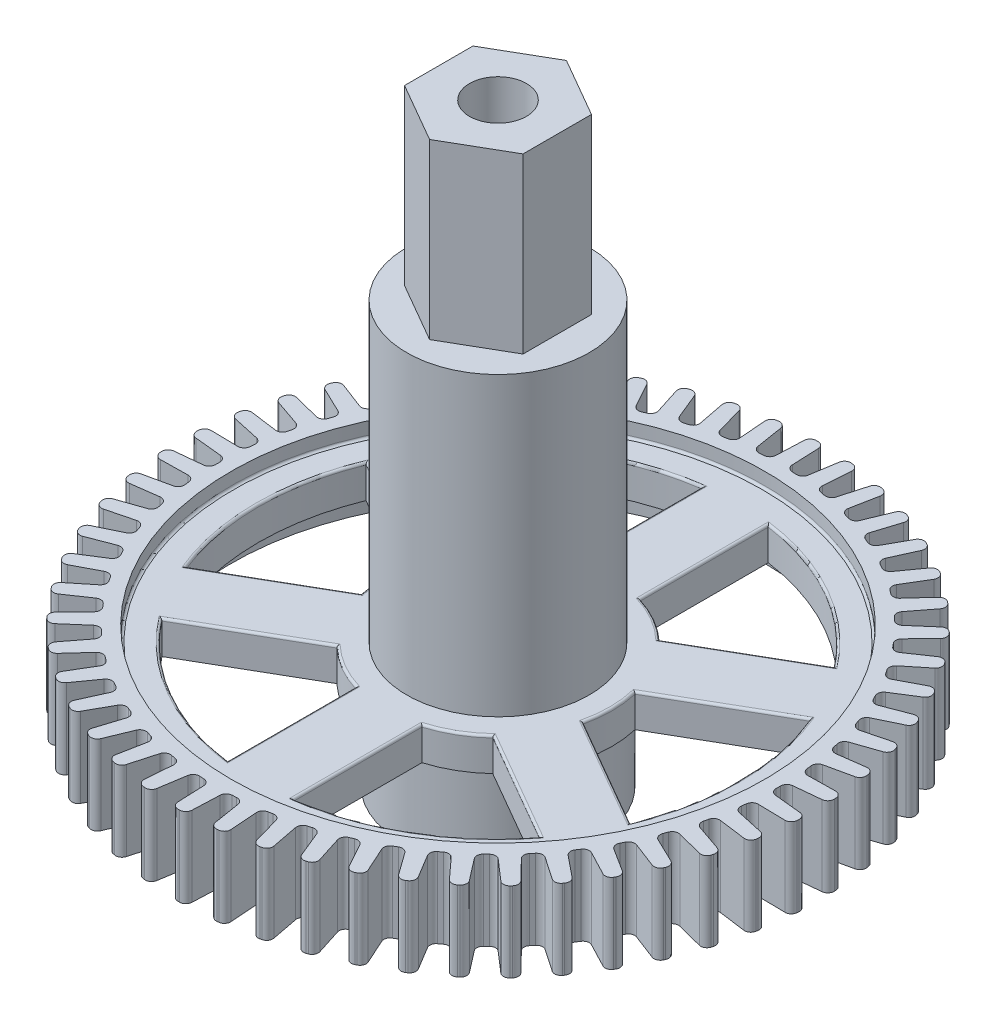
SolidWorks part; units mm, degrees
ref_plane "Plano frontal" through (0, 0, 0) normal (0, 0, 1) x (1, 0, 0)
ref_plane "Plano superior" through (0, 0, 0) normal (0, 1, 0) x (1, 0, 0)
ref_plane "Plano direito" through (0, 0, 0) normal (1, 0, 0) x (0, 0, -1)
sketch "Esboço1" plane through (0, 0, 0) normal (0, 1, 0) x (1, 0, 0)
  line L0 (0, 12.3) -> (0, 14) construction
  line L1 (-0.0361, 13.9968) -> (0.0361, 13.9968)
  line L2 (1.9031, 13.6041) -> (1.8135, 12.4166)
  line L3 (1.5891, 13.9063) -> (1.6608, 13.898)
  line L4 (1.2856, 13.6763) -> (1.0988, 12.5001)
  line L5 (0.6185, 12.28) -> (0.8112, 12.2687)
  line L6 (3.4695, 13.2912) -> (3.2427, 12.1221)
  line L7 (3.1928, 13.6278) -> (3.263, 13.6112)
  line L8 (2.8646, 13.4346) -> (2.5426, 12.2881)
  line L9 (-0.3108, 13.7331) -> (-0.3598, 12.5432)
  line L10 (0.3108, 13.7331) -> (0.3598, 12.5432)
  line L11 (0.37, 12.2944) -> (0.37, 12.2963)
  line L12 (2.04, 12.1251) -> (2.2301, 12.0916)
  line L13 (4.9891, 12.7986) -> (4.6281, 11.6637)
  line L14 (4.7533, 13.165) -> (4.8211, 13.1403)
  line L15 (4.4049, 13.0112) -> (3.952, 11.9098)
  line L16 (3.4338, 11.8063) -> (3.6187, 11.7509)
  line L17 (6.4412, 12.1328) -> (5.9509, 11.0475)
  line L18 (6.2495, 12.5242) -> (6.314, 12.4918)
  line L19 (5.8856, 12.4118) -> (5.3079, 11.3705)
  line L20 (4.7812, 11.3278) -> (4.9585, 11.2514)
  line L21 (7.8062, 11.303) -> (7.1932, 10.282)
  line L22 (7.6612, 11.714) -> (7.7215, 11.6743)
  line L23 (7.2867, 11.6446) -> (6.592, 10.6774)
  line L24 (6.064, 10.6962) -> (6.2312, 10.5997)
  line L25 (9.0656, 10.3203) -> (8.3382, 9.3774)
  line L26 (8.9693, 10.7453) -> (9.0246, 10.699)
  line L27 (8.5893, 10.72) -> (7.787, 9.8399)
  line L28 (7.2647, 9.9199) -> (7.4196, 9.8046)
  line L29 (10.2024, 9.1981) -> (9.3705, 8.346)
  line L30 (10.1561, 9.6314) -> (10.2056, 9.5789)
  line L31 (9.7758, 9.6503) -> (8.8767, 8.8693)
  line L32 (8.3672, 9.0094) -> (8.5076, 8.8769)
  line L33 (11.2012, 7.9515) -> (10.276, 7.2017)
  line L34 (11.2056, 8.3872) -> (11.2487, 8.3294)
  line L35 (10.83, 8.4502) -> (9.8463, 7.7789)
  line L36 (9.3566, 7.9771) -> (9.4807, 7.8292)
  line L37 (12.0486, 6.5973) -> (11.0426, 5.96)
  line L38 (12.1035, 7.0296) -> (12.1396, 6.9672)
  line L39 (11.7378, 7.1357) -> (10.6828, 6.5832)
  line L40 (10.2194, 6.8369) -> (10.3255, 6.6757)
  line L41 (12.7331, 5.154) -> (11.6599, 4.6378)
  line L42 (12.8378, 5.577) -> (12.8664, 5.5107)
  line L43 (12.4868, 5.7248) -> (11.3749, 5.2985)
  line L44 (10.944, 5.6043) -> (11.0307, 5.4318)
  line L45 (13.2453, 3.6409) -> (12.1194, 3.2528)
  line L46 (13.3984, 4.0489) -> (13.4191, 3.9798)
  line L47 (13.067, 4.2365) -> (11.9131, 3.9421)
  line L48 (11.5206, 4.2959) -> (11.5867, 4.1145)
  line L49 (13.5784, 2.0786) -> (12.4151, 1.8238)
  line L50 (13.7779, 2.466) -> (13.7904, 2.395)
  line L51 (13.4705, 2.6908) -> (12.2902, 2.5324)
  line L52 (11.9415, 2.9294) -> (11.986, 2.7415)
  line L53 (13.7279, 0.4882) -> (12.5429, 0.3702)
  line L54 (13.971, 0.8499) -> (13.9752, 0.7778)
  line L55 (13.6918, 1.1088) -> (12.5011, 1.0885)
  line L56 (12.2008, 1.5232) -> (12.2232, 1.3315)
  line L57 (13.6918, -1.1088) -> (12.5011, -1.0885)
  line L58 (13.9752, -0.7778) -> (13.971, -0.8499)
  line L59 (13.7279, -0.4882) -> (12.5429, -0.3702)
  line L60 (12.2951, 0.0965) -> (12.2951, -0.0965)
  line L61 (13.4705, -2.6908) -> (12.2902, -2.5324)
  line L62 (13.7904, -2.395) -> (13.7779, -2.466)
  line L63 (13.5784, -2.0786) -> (12.4151, -1.8238)
  line L64 (12.2232, -1.3315) -> (12.2008, -1.5232)
  line L65 (13.067, -4.2365) -> (11.9131, -3.9421)
  line L66 (13.4191, -3.9798) -> (13.3984, -4.0489)
  line L67 (13.2453, -3.6409) -> (12.1194, -3.2528)
  line L68 (11.986, -2.7415) -> (11.9415, -2.9294)
  line L69 (12.4868, -5.7248) -> (11.3749, -5.2985)
  line L70 (12.8664, -5.5107) -> (12.8378, -5.577)
  line L71 (12.7331, -5.154) -> (11.6599, -4.6378)
  line L72 (11.5867, -4.1145) -> (11.5206, -4.2959)
  line L73 (11.7378, -7.1357) -> (10.6828, -6.5832)
  line L74 (12.1396, -6.9672) -> (12.1035, -7.0296)
  line L75 (12.0486, -6.5973) -> (11.0426, -5.96)
  line L76 (11.0307, -5.4318) -> (10.944, -5.6043)
  line L77 (10.83, -8.4502) -> (9.8463, -7.7789)
  line L78 (11.2487, -8.3294) -> (11.2056, -8.3872)
  line L79 (11.2012, -7.9515) -> (10.276, -7.2017)
  line L80 (10.3255, -6.6757) -> (10.2194, -6.8369)
  line L81 (9.7758, -9.6503) -> (8.8767, -8.8693)
  line L82 (10.2056, -9.5789) -> (10.1561, -9.6314)
  line L83 (10.2024, -9.1981) -> (9.3705, -8.346)
  line L84 (9.4807, -7.8292) -> (9.3566, -7.9771)
  line L85 (8.5893, -10.72) -> (7.787, -9.8399)
  line L86 (9.0246, -10.699) -> (8.9693, -10.7453)
  line L87 (9.0656, -10.3203) -> (8.3382, -9.3774)
  line L88 (8.5076, -8.8769) -> (8.3672, -9.0094)
  line L89 (7.2867, -11.6446) -> (6.592, -10.6774)
  line L90 (7.7215, -11.6743) -> (7.6612, -11.714)
  line L91 (7.8062, -11.303) -> (7.1932, -10.282)
  line L92 (7.4196, -9.8046) -> (7.2647, -9.9199)
  line L93 (5.8856, -12.4118) -> (5.3079, -11.3705)
  line L94 (6.314, -12.4918) -> (6.2495, -12.5242)
  line L95 (6.4412, -12.1328) -> (5.9509, -11.0475)
  line L96 (6.2312, -10.5997) -> (6.064, -10.6962)
  line L97 (4.4049, -13.0112) -> (3.952, -11.9098)
  line L98 (4.8211, -13.1403) -> (4.7533, -13.165)
  line L99 (4.9891, -12.7986) -> (4.6281, -11.6637)
  line L100 (4.9585, -11.2514) -> (4.7812, -11.3278)
  line L101 (2.8646, -13.4346) -> (2.5426, -12.2881)
  line L102 (3.263, -13.6112) -> (3.1928, -13.6278)
  line L103 (3.4695, -13.2912) -> (3.2427, -12.1221)
  line L104 (3.6187, -11.7509) -> (3.4338, -11.8063)
  line L105 (1.2856, -13.6763) -> (1.0988, -12.5001)
  line L106 (1.6608, -13.898) -> (1.5891, -13.9063)
  line L107 (1.9031, -13.6041) -> (1.8135, -12.4166)
  line L108 (2.2301, -12.0916) -> (2.04, -12.1251)
  line L109 (-0.3108, -13.7331) -> (-0.3598, -12.5432)
  line L110 (0.0361, -13.9968) -> (-0.0361, -13.9968)
  line L111 (0.3108, -13.7331) -> (0.3598, -12.5432)
  line L112 (0.8112, -12.2687) -> (0.6185, -12.28)
  line L113 (-1.9031, -13.6041) -> (-1.8135, -12.4166)
  line L114 (-1.5891, -13.9063) -> (-1.6608, -13.898)
  line L115 (-1.2856, -13.6763) -> (-1.0988, -12.5001)
  line L116 (-0.6185, -12.28) -> (-0.8112, -12.2687)
  line L117 (-3.4695, -13.2912) -> (-3.2427, -12.1221)
  line L118 (-3.1928, -13.6278) -> (-3.263, -13.6112)
  line L119 (-2.8646, -13.4346) -> (-2.5426, -12.2881)
  line L120 (-2.04, -12.1251) -> (-2.2301, -12.0916)
  line L121 (-4.9891, -12.7986) -> (-4.6281, -11.6637)
  line L122 (-4.7533, -13.165) -> (-4.8211, -13.1403)
  line L123 (-4.4049, -13.0112) -> (-3.952, -11.9098)
  line L124 (-3.4338, -11.8063) -> (-3.6187, -11.7509)
  line L125 (-6.4412, -12.1328) -> (-5.9509, -11.0475)
  line L126 (-6.2495, -12.5242) -> (-6.314, -12.4918)
  line L127 (-5.8856, -12.4118) -> (-5.3079, -11.3705)
  line L128 (-4.7812, -11.3278) -> (-4.9585, -11.2514)
  line L129 (-7.8062, -11.303) -> (-7.1932, -10.282)
  line L130 (-7.6612, -11.714) -> (-7.7215, -11.6743)
  line L131 (-7.2867, -11.6446) -> (-6.592, -10.6774)
  line L132 (-6.064, -10.6962) -> (-6.2312, -10.5997)
  line L133 (-9.0656, -10.3203) -> (-8.3382, -9.3774)
  line L134 (-8.9693, -10.7453) -> (-9.0246, -10.699)
  line L135 (-8.5893, -10.72) -> (-7.787, -9.8399)
  line L136 (-7.2647, -9.9199) -> (-7.4196, -9.8046)
  line L137 (-10.2024, -9.1981) -> (-9.3705, -8.346)
  line L138 (-10.1561, -9.6314) -> (-10.2056, -9.5789)
  line L139 (-9.7758, -9.6503) -> (-8.8767, -8.8693)
  line L140 (-8.3672, -9.0094) -> (-8.5076, -8.8769)
  line L141 (-11.2012, -7.9515) -> (-10.276, -7.2017)
  line L142 (-11.2056, -8.3872) -> (-11.2487, -8.3294)
  line L143 (-10.83, -8.4502) -> (-9.8463, -7.7789)
  line L144 (-9.3566, -7.9771) -> (-9.4807, -7.8292)
  line L145 (-12.0486, -6.5973) -> (-11.0426, -5.96)
  line L146 (-12.1035, -7.0296) -> (-12.1396, -6.9672)
  line L147 (-11.7378, -7.1357) -> (-10.6828, -6.5832)
  line L148 (-10.2194, -6.8369) -> (-10.3255, -6.6757)
  line L149 (-12.7331, -5.154) -> (-11.6599, -4.6378)
  line L150 (-12.8378, -5.577) -> (-12.8664, -5.5107)
  line L151 (-12.4868, -5.7248) -> (-11.3749, -5.2985)
  line L152 (-10.944, -5.6043) -> (-11.0307, -5.4318)
  line L153 (-13.2453, -3.6409) -> (-12.1194, -3.2528)
  line L154 (-13.3984, -4.0489) -> (-13.4191, -3.9798)
  line L155 (-13.067, -4.2365) -> (-11.9131, -3.9421)
  line L156 (-11.5206, -4.2959) -> (-11.5867, -4.1145)
  line L157 (-13.5784, -2.0786) -> (-12.4151, -1.8238)
  line L158 (-13.7779, -2.466) -> (-13.7904, -2.395)
  line L159 (-13.4705, -2.6908) -> (-12.2902, -2.5324)
  line L160 (-11.9415, -2.9294) -> (-11.986, -2.7415)
  line L161 (-13.7279, -0.4882) -> (-12.5429, -0.3702)
  line L162 (-13.971, -0.8499) -> (-13.9752, -0.7778)
  line L163 (-13.6918, -1.1088) -> (-12.5011, -1.0885)
  line L164 (-0.8112, 12.2687) -> (-0.6185, 12.28)
  line L165 (-12.2008, -1.5232) -> (-12.2232, -1.3315)
  line L166 (-13.6918, 1.1088) -> (-12.5011, 1.0885)
  line L167 (-13.9752, 0.7778) -> (-13.971, 0.8499)
  line L168 (-13.7279, 0.4882) -> (-12.5429, 0.3702)
  line L169 (-12.2951, -0.0965) -> (-12.2951, 0.0965)
  line L170 (-13.4705, 2.6908) -> (-12.2902, 2.5324)
  line L171 (-13.7904, 2.395) -> (-13.7779, 2.466)
  line L172 (-13.5784, 2.0786) -> (-12.4151, 1.8238)
  line L173 (-12.2232, 1.3315) -> (-12.2008, 1.5232)
  line L174 (-13.067, 4.2365) -> (-11.9131, 3.9421)
  line L175 (-13.4191, 3.9798) -> (-13.3984, 4.0489)
  line L176 (-13.2453, 3.6409) -> (-12.1194, 3.2528)
  line L177 (-11.986, 2.7415) -> (-11.9415, 2.9294)
  line L178 (-12.4868, 5.7248) -> (-11.3749, 5.2985)
  line L179 (-12.8664, 5.5107) -> (-12.8378, 5.577)
  line L180 (-12.7331, 5.154) -> (-11.6599, 4.6378)
  line L181 (-11.5867, 4.1145) -> (-11.5206, 4.2959)
  line L182 (-11.7378, 7.1357) -> (-10.6828, 6.5832)
  line L183 (-12.1396, 6.9672) -> (-12.1035, 7.0296)
  line L184 (-12.0486, 6.5973) -> (-11.0426, 5.96)
  line L185 (-11.0307, 5.4318) -> (-10.944, 5.6043)
  line L186 (-10.83, 8.4502) -> (-9.8463, 7.7789)
  line L187 (-11.2487, 8.3294) -> (-11.2056, 8.3872)
  line L188 (-11.2012, 7.9515) -> (-10.276, 7.2017)
  line L189 (-10.3255, 6.6757) -> (-10.2194, 6.8369)
  line L190 (-9.7758, 9.6503) -> (-8.8767, 8.8693)
  line L191 (-10.2056, 9.5789) -> (-10.1561, 9.6314)
  line L192 (-10.2024, 9.1981) -> (-9.3705, 8.346)
  line L193 (-9.4807, 7.8292) -> (-9.3566, 7.9771)
  line L194 (-8.5893, 10.72) -> (-7.787, 9.8399)
  line L195 (-9.0246, 10.699) -> (-8.9693, 10.7453)
  line L196 (-9.0656, 10.3203) -> (-8.3382, 9.3774)
  line L197 (-8.5076, 8.8769) -> (-8.3672, 9.0094)
  line L198 (-7.2867, 11.6446) -> (-6.592, 10.6774)
  line L199 (-7.7215, 11.6743) -> (-7.6612, 11.714)
  line L200 (-7.8062, 11.303) -> (-7.1932, 10.282)
  line L201 (-7.4196, 9.8046) -> (-7.2647, 9.9199)
  line L202 (-5.8856, 12.4118) -> (-5.3079, 11.3705)
  line L203 (-6.314, 12.4918) -> (-6.2495, 12.5242)
  line L204 (-6.4412, 12.1328) -> (-5.9509, 11.0475)
  line L205 (-6.2312, 10.5997) -> (-6.064, 10.6962)
  line L206 (-4.4049, 13.0112) -> (-3.952, 11.9098)
  line L207 (-4.8211, 13.1403) -> (-4.7533, 13.165)
  line L208 (-4.9891, 12.7986) -> (-4.6281, 11.6637)
  line L209 (-4.9585, 11.2514) -> (-4.7812, 11.3278)
  line L210 (-2.8646, 13.4346) -> (-2.5426, 12.2881)
  line L211 (-3.263, 13.6112) -> (-3.1928, 13.6278)
  line L212 (-3.4695, 13.2912) -> (-3.2427, 12.1221)
  line L213 (-3.6187, 11.7509) -> (-3.4338, 11.8063)
  line L214 (-1.2856, 13.6763) -> (-1.0988, 12.5001)
  line L215 (-1.6608, 13.898) -> (-1.5891, 13.9063)
  line L216 (-1.9031, 13.6041) -> (-1.8135, 12.4166)
  line L217 (-2.2301, 12.0916) -> (-2.04, 12.1251)
  arc A0 (0.3108, 13.7331) -> (0.0361, 13.9968) centre (0.0361, 13.7218) ccw
  arc A1 (-0.8112, 12.2687) -> (-1.0988, 12.5001) centre (-0.8272, 12.5433) cw
  arc A2 (-0.3108, 13.7331) -> (-0.0361, 13.9968) centre (-0.0361, 13.7218) cw
  arc A3 (1.9031, 13.6041) -> (1.6608, 13.898) centre (1.6288, 13.6248) ccw
  arc A4 (1.2856, 13.6763) -> (1.5891, 13.9063) centre (1.5572, 13.6332) cw
  arc A5 (1.0988, 12.5001) -> (0.8112, 12.2687) centre (0.8272, 12.5433) cw
  arc A6 (0.6185, 12.28) -> (0.3598, 12.5432) centre (0.6345, 12.5545) cw
  arc A7 (3.4695, 13.2912) -> (3.263, 13.6112) centre (3.1996, 13.3436) ccw
  arc A8 (2.8646, 13.4346) -> (3.1928, 13.6278) centre (3.1294, 13.3602) cw
  arc A9 (2.5426, 12.2881) -> (2.2301, 12.0916) centre (2.2778, 12.3624) cw
  arc A10 (2.04, 12.1251) -> (1.8135, 12.4166) centre (2.0877, 12.3959) cw
  arc A11 (4.9891, 12.7986) -> (4.8211, 13.1403) centre (4.727, 12.8819) ccw
  arc A12 (4.4049, 13.0112) -> (4.7533, 13.165) centre (4.6592, 12.9066) cw
  arc A13 (3.952, 11.9098) -> (3.6187, 11.7509) centre (3.6976, 12.0144) cw
  arc A14 (3.4338, 11.8063) -> (3.2427, 12.1221) centre (3.5127, 12.0697) cw
  arc A15 (6.4412, 12.1328) -> (6.314, 12.4918) centre (6.1906, 12.246) ccw
  arc A16 (5.8856, 12.4118) -> (6.2495, 12.5242) centre (6.1261, 12.2784) cw
  arc A17 (5.3079, 11.3705) -> (4.9585, 11.2514) centre (5.0674, 11.5039) cw
  arc A18 (4.7812, 11.3278) -> (4.6281, 11.6637) centre (4.8902, 11.5803) cw
  arc A19 (7.8062, 11.303) -> (7.7215, 11.6743) centre (7.5704, 11.4446) ccw
  arc A20 (7.2867, 11.6446) -> (7.6612, 11.714) centre (7.5101, 11.4842) cw
  arc A21 (6.592, 10.6774) -> (6.2312, 10.5997) centre (6.3687, 10.8378) cw
  arc A22 (6.064, 10.6962) -> (5.9509, 11.0475) centre (6.2015, 10.9343) cw
  arc A23 (9.0656, 10.3203) -> (9.0246, 10.699) centre (8.8478, 10.4883) ccw
  arc A24 (8.5893, 10.72) -> (8.9693, 10.7453) centre (8.7926, 10.5347) cw
  arc A25 (7.787, 9.8399) -> (7.4196, 9.8046) centre (7.5838, 10.0252) cw
  arc A26 (7.2647, 9.9199) -> (7.1932, 10.282) centre (7.429, 10.1404) cw
  arc A27 (10.2024, 9.1981) -> (10.2056, 9.5789) centre (10.0056, 9.3902) ccw
  arc A28 (9.7758, 9.6503) -> (10.1561, 9.6314) centre (9.9561, 9.4427) cw
  arc A29 (8.8767, 8.8693) -> (8.5076, 8.8769) centre (8.6964, 9.077) cw
  arc A30 (8.3672, 9.0094) -> (8.3382, 9.3774) centre (8.556, 9.2094) cw
  arc A31 (11.2012, 7.9515) -> (11.2487, 8.3294) centre (11.0281, 8.1651) ccw
  arc A32 (10.83, 8.4502) -> (11.2056, 8.3872) centre (10.985, 8.223) cw
  arc A33 (9.8463, 7.7789) -> (9.4807, 7.8292) centre (9.6913, 8.006) cw
  arc A34 (9.3566, 7.9771) -> (9.3705, 8.346) centre (9.5673, 8.1539) cw
  arc A35 (12.0486, 6.5973) -> (12.1396, 6.9672) centre (11.9015, 6.8297) ccw
  arc A36 (11.7378, 7.1357) -> (12.1035, 7.0296) centre (11.8654, 6.8921) cw
  arc A37 (10.6828, 6.5832) -> (10.3255, 6.6757) centre (10.5552, 6.8268) cw
  arc A38 (10.2194, 6.8369) -> (10.276, 7.2017) centre (10.4492, 6.988) cw
  arc A39 (12.7331, 5.154) -> (12.8664, 5.5107) centre (12.6139, 5.4018) ccw
  arc A40 (12.4868, 5.7248) -> (12.8378, 5.577) centre (12.5853, 5.468) cw
  arc A41 (11.3749, 5.2985) -> (11.0307, 5.4318) centre (11.2764, 5.5552) cw
  arc A42 (10.944, 5.6043) -> (11.0426, 5.96) centre (11.1898, 5.7277) cw
  arc A43 (13.2453, 3.6409) -> (13.4191, 3.9798) centre (13.1557, 3.9009) ccw
  arc A44 (13.067, 4.2365) -> (13.3984, 4.0489) centre (13.135, 3.97) cw
  arc A45 (11.9131, 3.9421) -> (11.5867, 4.1145) centre (11.8451, 4.2086) cw
  arc A46 (11.5206, 4.2959) -> (11.6599, 4.6378) centre (11.7791, 4.3899) cw
  arc A47 (13.5784, 2.0786) -> (13.7904, 2.395) centre (13.5196, 2.3472) ccw
  arc A48 (13.4705, 2.6908) -> (13.7779, 2.466) centre (13.5071, 2.4183) cw
  arc A49 (12.2902, 2.5324) -> (11.986, 2.7415) centre (12.2536, 2.805) cw
  arc A50 (11.9415, 2.9294) -> (12.1194, 3.2528) centre (12.2091, 2.9928) cw
  arc A51 (13.7279, 0.4882) -> (13.9752, 0.7778) centre (13.7007, 0.7618) ccw
  arc A52 (13.6918, 1.1088) -> (13.971, 0.8499) centre (13.6965, 0.8339) cw
  arc A53 (12.5011, 1.0885) -> (12.2232, 1.3315) centre (12.4964, 1.3634) cw
  arc A54 (12.2008, 1.5232) -> (12.4151, 1.8238) centre (12.4739, 1.5552) cw
  arc A55 (13.6918, -1.1088) -> (13.971, -0.8499) centre (13.6965, -0.8339) ccw
  arc A56 (13.7279, -0.4882) -> (13.9752, -0.7778) centre (13.7007, -0.7618) cw
  arc A57 (12.5429, -0.3702) -> (12.2951, -0.0965) centre (12.5701, -0.0965) cw
  arc A58 (12.2951, 0.0965) -> (12.5429, 0.3702) centre (12.5701, 0.0965) cw
  arc A59 (13.4705, -2.6908) -> (13.7779, -2.466) centre (13.5071, -2.4183) ccw
  arc A60 (13.5784, -2.0786) -> (13.7904, -2.395) centre (13.5196, -2.3472) cw
  arc A61 (12.4151, -1.8238) -> (12.2008, -1.5232) centre (12.4739, -1.5552) cw
  arc A62 (12.2232, -1.3315) -> (12.5011, -1.0885) centre (12.4964, -1.3634) cw
  arc A63 (13.067, -4.2365) -> (13.3984, -4.0489) centre (13.135, -3.97) ccw
  arc A64 (13.2453, -3.6409) -> (13.4191, -3.9798) centre (13.1557, -3.9009) cw
  arc A65 (12.1194, -3.2528) -> (11.9415, -2.9294) centre (12.2091, -2.9928) cw
  arc A66 (11.986, -2.7415) -> (12.2902, -2.5324) centre (12.2536, -2.805) cw
  arc A67 (12.4868, -5.7248) -> (12.8378, -5.577) centre (12.5853, -5.468) ccw
  arc A68 (12.7331, -5.154) -> (12.8664, -5.5107) centre (12.6139, -5.4018) cw
  arc A69 (11.6599, -4.6378) -> (11.5206, -4.2959) centre (11.7791, -4.3899) cw
  arc A70 (11.5867, -4.1145) -> (11.9131, -3.9421) centre (11.8451, -4.2086) cw
  arc A71 (11.7378, -7.1357) -> (12.1035, -7.0296) centre (11.8654, -6.8921) ccw
  arc A72 (12.0486, -6.5973) -> (12.1396, -6.9672) centre (11.9015, -6.8297) cw
  arc A73 (11.0426, -5.96) -> (10.944, -5.6043) centre (11.1898, -5.7277) cw
  arc A74 (11.0307, -5.4318) -> (11.3749, -5.2985) centre (11.2764, -5.5552) cw
  arc A75 (10.83, -8.4502) -> (11.2056, -8.3872) centre (10.985, -8.223) ccw
  arc A76 (11.2012, -7.9515) -> (11.2487, -8.3294) centre (11.0281, -8.1651) cw
  arc A77 (10.276, -7.2017) -> (10.2194, -6.8369) centre (10.4492, -6.988) cw
  arc A78 (10.3255, -6.6757) -> (10.6828, -6.5832) centre (10.5552, -6.8268) cw
  arc A79 (9.7758, -9.6503) -> (10.1561, -9.6314) centre (9.9561, -9.4427) ccw
  arc A80 (10.2024, -9.1981) -> (10.2056, -9.5789) centre (10.0056, -9.3902) cw
  arc A81 (9.3705, -8.346) -> (9.3566, -7.9771) centre (9.5673, -8.1539) cw
  arc A82 (9.4807, -7.8292) -> (9.8463, -7.7789) centre (9.6913, -8.006) cw
  arc A83 (8.5893, -10.72) -> (8.9693, -10.7453) centre (8.7926, -10.5347) ccw
  arc A84 (9.0656, -10.3203) -> (9.0246, -10.699) centre (8.8478, -10.4883) cw
  arc A85 (8.3382, -9.3774) -> (8.3672, -9.0094) centre (8.556, -9.2094) cw
  arc A86 (8.5076, -8.8769) -> (8.8767, -8.8693) centre (8.6964, -9.077) cw
  arc A87 (7.2867, -11.6446) -> (7.6612, -11.714) centre (7.5101, -11.4842) ccw
  arc A88 (7.8062, -11.303) -> (7.7215, -11.6743) centre (7.5704, -11.4446) cw
  arc A89 (7.1932, -10.282) -> (7.2647, -9.9199) centre (7.429, -10.1404) cw
  arc A90 (7.4196, -9.8046) -> (7.787, -9.8399) centre (7.5838, -10.0252) cw
  arc A91 (5.8856, -12.4118) -> (6.2495, -12.5242) centre (6.1261, -12.2784) ccw
  arc A92 (6.4412, -12.1328) -> (6.314, -12.4918) centre (6.1906, -12.246) cw
  arc A93 (5.9509, -11.0475) -> (6.064, -10.6962) centre (6.2015, -10.9343) cw
  arc A94 (6.2312, -10.5997) -> (6.592, -10.6774) centre (6.3687, -10.8378) cw
  arc A95 (4.4049, -13.0112) -> (4.7533, -13.165) centre (4.6592, -12.9066) ccw
  arc A96 (4.9891, -12.7986) -> (4.8211, -13.1403) centre (4.727, -12.8819) cw
  arc A97 (4.6281, -11.6637) -> (4.7812, -11.3278) centre (4.8902, -11.5803) cw
  arc A98 (4.9585, -11.2514) -> (5.3079, -11.3705) centre (5.0674, -11.5039) cw
  arc A99 (2.8646, -13.4346) -> (3.1928, -13.6278) centre (3.1294, -13.3602) ccw
  arc A100 (3.4695, -13.2912) -> (3.263, -13.6112) centre (3.1996, -13.3436) cw
  arc A101 (3.2427, -12.1221) -> (3.4338, -11.8063) centre (3.5127, -12.0697) cw
  arc A102 (3.6187, -11.7509) -> (3.952, -11.9098) centre (3.6976, -12.0144) cw
  arc A103 (1.2856, -13.6763) -> (1.5891, -13.9063) centre (1.5572, -13.6332) ccw
  arc A104 (1.9031, -13.6041) -> (1.6608, -13.898) centre (1.6288, -13.6248) cw
  arc A105 (1.8135, -12.4166) -> (2.04, -12.1251) centre (2.0877, -12.3959) cw
  arc A106 (2.2301, -12.0916) -> (2.5426, -12.2881) centre (2.2778, -12.3624) cw
  arc A107 (-0.3108, -13.7331) -> (-0.0361, -13.9968) centre (-0.0361, -13.7218) ccw
  arc A108 (0.3108, -13.7331) -> (0.0361, -13.9968) centre (0.0361, -13.7218) cw
  arc A109 (-0.3598, 12.5432) -> (-0.6185, 12.28) centre (-0.6345, 12.5545) cw
  arc A110 (0.3598, -12.5432) -> (0.6185, -12.28) centre (0.6345, -12.5545) cw
  arc A111 (0.8112, -12.2687) -> (1.0988, -12.5001) centre (0.8272, -12.5433) cw
  arc A112 (-1.9031, -13.6041) -> (-1.6608, -13.898) centre (-1.6288, -13.6248) ccw
  arc A113 (-1.2856, -13.6763) -> (-1.5891, -13.9063) centre (-1.5572, -13.6332) cw
  arc A114 (-1.0988, -12.5001) -> (-0.8112, -12.2687) centre (-0.8272, -12.5433) cw
  arc A115 (-0.6185, -12.28) -> (-0.3598, -12.5432) centre (-0.6345, -12.5545) cw
  arc A116 (-3.4695, -13.2912) -> (-3.263, -13.6112) centre (-3.1996, -13.3436) ccw
  arc A117 (-2.8646, -13.4346) -> (-3.1928, -13.6278) centre (-3.1294, -13.3602) cw
  arc A118 (-2.5426, -12.2881) -> (-2.2301, -12.0916) centre (-2.2778, -12.3624) cw
  arc A119 (-2.04, -12.1251) -> (-1.8135, -12.4166) centre (-2.0877, -12.3959) cw
  arc A120 (-4.9891, -12.7986) -> (-4.8211, -13.1403) centre (-4.727, -12.8819) ccw
  arc A121 (-4.4049, -13.0112) -> (-4.7533, -13.165) centre (-4.6592, -12.9066) cw
  arc A122 (-3.952, -11.9098) -> (-3.6187, -11.7509) centre (-3.6976, -12.0144) cw
  arc A123 (-3.4338, -11.8063) -> (-3.2427, -12.1221) centre (-3.5127, -12.0697) cw
  arc A124 (-6.4412, -12.1328) -> (-6.314, -12.4918) centre (-6.1906, -12.246) ccw
  arc A125 (-5.8856, -12.4118) -> (-6.2495, -12.5242) centre (-6.1261, -12.2784) cw
  arc A126 (-5.3079, -11.3705) -> (-4.9585, -11.2514) centre (-5.0674, -11.5039) cw
  arc A127 (-4.7812, -11.3278) -> (-4.6281, -11.6637) centre (-4.8902, -11.5803) cw
  arc A128 (-7.8062, -11.303) -> (-7.7215, -11.6743) centre (-7.5704, -11.4446) ccw
  arc A129 (-7.2867, -11.6446) -> (-7.6612, -11.714) centre (-7.5101, -11.4842) cw
  arc A130 (-6.592, -10.6774) -> (-6.2312, -10.5997) centre (-6.3687, -10.8378) cw
  arc A131 (-6.064, -10.6962) -> (-5.9509, -11.0475) centre (-6.2015, -10.9343) cw
  arc A132 (-9.0656, -10.3203) -> (-9.0246, -10.699) centre (-8.8478, -10.4883) ccw
  arc A133 (-8.5893, -10.72) -> (-8.9693, -10.7453) centre (-8.7926, -10.5347) cw
  arc A134 (-7.787, -9.8399) -> (-7.4196, -9.8046) centre (-7.5838, -10.0252) cw
  arc A135 (-7.2647, -9.9199) -> (-7.1932, -10.282) centre (-7.429, -10.1404) cw
  arc A136 (-10.2024, -9.1981) -> (-10.2056, -9.5789) centre (-10.0056, -9.3902) ccw
  arc A137 (-9.7758, -9.6503) -> (-10.1561, -9.6314) centre (-9.9561, -9.4427) cw
  arc A138 (-8.8767, -8.8693) -> (-8.5076, -8.8769) centre (-8.6964, -9.077) cw
  arc A139 (-8.3672, -9.0094) -> (-8.3382, -9.3774) centre (-8.556, -9.2094) cw
  arc A140 (-11.2012, -7.9515) -> (-11.2487, -8.3294) centre (-11.0281, -8.1651) ccw
  arc A141 (-10.83, -8.4502) -> (-11.2056, -8.3872) centre (-10.985, -8.223) cw
  arc A142 (-9.8463, -7.7789) -> (-9.4807, -7.8292) centre (-9.6913, -8.006) cw
  arc A143 (-9.3566, -7.9771) -> (-9.3705, -8.346) centre (-9.5673, -8.1539) cw
  arc A144 (-12.0486, -6.5973) -> (-12.1396, -6.9672) centre (-11.9015, -6.8297) ccw
  arc A145 (-11.7378, -7.1357) -> (-12.1035, -7.0296) centre (-11.8654, -6.8921) cw
  arc A146 (-10.6828, -6.5832) -> (-10.3255, -6.6757) centre (-10.5552, -6.8268) cw
  arc A147 (-10.2194, -6.8369) -> (-10.276, -7.2017) centre (-10.4492, -6.988) cw
  arc A148 (-12.7331, -5.154) -> (-12.8664, -5.5107) centre (-12.6139, -5.4018) ccw
  arc A149 (-12.4868, -5.7248) -> (-12.8378, -5.577) centre (-12.5853, -5.468) cw
  arc A150 (-11.3749, -5.2985) -> (-11.0307, -5.4318) centre (-11.2764, -5.5552) cw
  arc A151 (-10.944, -5.6043) -> (-11.0426, -5.96) centre (-11.1898, -5.7277) cw
  arc A152 (-13.2453, -3.6409) -> (-13.4191, -3.9798) centre (-13.1557, -3.9009) ccw
  arc A153 (-13.067, -4.2365) -> (-13.3984, -4.0489) centre (-13.135, -3.97) cw
  arc A154 (-11.9131, -3.9421) -> (-11.5867, -4.1145) centre (-11.8451, -4.2086) cw
  arc A155 (-11.5206, -4.2959) -> (-11.6599, -4.6378) centre (-11.7791, -4.3899) cw
  arc A156 (-13.5784, -2.0786) -> (-13.7904, -2.395) centre (-13.5196, -2.3472) ccw
  arc A157 (-13.4705, -2.6908) -> (-13.7779, -2.466) centre (-13.5071, -2.4183) cw
  arc A158 (-12.2902, -2.5324) -> (-11.986, -2.7415) centre (-12.2536, -2.805) cw
  arc A159 (-11.9415, -2.9294) -> (-12.1194, -3.2528) centre (-12.2091, -2.9928) cw
  arc A160 (-13.7279, -0.4882) -> (-13.9752, -0.7778) centre (-13.7007, -0.7618) ccw
  arc A161 (-13.6918, -1.1088) -> (-13.971, -0.8499) centre (-13.6965, -0.8339) cw
  arc A162 (-12.5011, -1.0885) -> (-12.2232, -1.3315) centre (-12.4964, -1.3634) cw
  arc A163 (-12.2008, -1.5232) -> (-12.4151, -1.8238) centre (-12.4739, -1.5552) cw
  arc A164 (-13.6918, 1.1088) -> (-13.971, 0.8499) centre (-13.6965, 0.8339) ccw
  arc A165 (-13.7279, 0.4882) -> (-13.9752, 0.7778) centre (-13.7007, 0.7618) cw
  arc A166 (-12.5429, 0.3702) -> (-12.2951, 0.0965) centre (-12.5701, 0.0965) cw
  arc A167 (-12.2951, -0.0965) -> (-12.5429, -0.3702) centre (-12.5701, -0.0965) cw
  arc A168 (-13.4705, 2.6908) -> (-13.7779, 2.466) centre (-13.5071, 2.4183) ccw
  arc A169 (-13.5784, 2.0786) -> (-13.7904, 2.395) centre (-13.5196, 2.3472) cw
  arc A170 (-12.4151, 1.8238) -> (-12.2008, 1.5232) centre (-12.4739, 1.5552) cw
  arc A171 (-12.2232, 1.3315) -> (-12.5011, 1.0885) centre (-12.4964, 1.3634) cw
  arc A172 (-13.067, 4.2365) -> (-13.3984, 4.0489) centre (-13.135, 3.97) ccw
  arc A173 (-13.2453, 3.6409) -> (-13.4191, 3.9798) centre (-13.1557, 3.9009) cw
  arc A174 (-12.1194, 3.2528) -> (-11.9415, 2.9294) centre (-12.2091, 2.9928) cw
  arc A175 (-11.986, 2.7415) -> (-12.2902, 2.5324) centre (-12.2536, 2.805) cw
  arc A176 (-12.4868, 5.7248) -> (-12.8378, 5.577) centre (-12.5853, 5.468) ccw
  arc A177 (-12.7331, 5.154) -> (-12.8664, 5.5107) centre (-12.6139, 5.4018) cw
  arc A178 (-11.6599, 4.6378) -> (-11.5206, 4.2959) centre (-11.7791, 4.3899) cw
  arc A179 (-11.5867, 4.1145) -> (-11.9131, 3.9421) centre (-11.8451, 4.2086) cw
  arc A180 (-11.7378, 7.1357) -> (-12.1035, 7.0296) centre (-11.8654, 6.8921) ccw
  arc A181 (-12.0486, 6.5973) -> (-12.1396, 6.9672) centre (-11.9015, 6.8297) cw
  arc A182 (-11.0426, 5.96) -> (-10.944, 5.6043) centre (-11.1898, 5.7277) cw
  arc A183 (-11.0307, 5.4318) -> (-11.3749, 5.2985) centre (-11.2764, 5.5552) cw
  arc A184 (-10.83, 8.4502) -> (-11.2056, 8.3872) centre (-10.985, 8.223) ccw
  arc A185 (-11.2012, 7.9515) -> (-11.2487, 8.3294) centre (-11.0281, 8.1651) cw
  arc A186 (-10.276, 7.2017) -> (-10.2194, 6.8369) centre (-10.4492, 6.988) cw
  arc A187 (-10.3255, 6.6757) -> (-10.6828, 6.5832) centre (-10.5552, 6.8268) cw
  arc A188 (-9.7758, 9.6503) -> (-10.1561, 9.6314) centre (-9.9561, 9.4427) ccw
  arc A189 (-10.2024, 9.1981) -> (-10.2056, 9.5789) centre (-10.0056, 9.3902) cw
  arc A190 (-9.3705, 8.346) -> (-9.3566, 7.9771) centre (-9.5673, 8.1539) cw
  arc A191 (-9.4807, 7.8292) -> (-9.8463, 7.7789) centre (-9.6913, 8.006) cw
  arc A192 (-8.5893, 10.72) -> (-8.9693, 10.7453) centre (-8.7926, 10.5347) ccw
  arc A193 (-9.0656, 10.3203) -> (-9.0246, 10.699) centre (-8.8478, 10.4883) cw
  arc A194 (-8.3382, 9.3774) -> (-8.3672, 9.0094) centre (-8.556, 9.2094) cw
  arc A195 (-8.5076, 8.8769) -> (-8.8767, 8.8693) centre (-8.6964, 9.077) cw
  arc A196 (-7.2867, 11.6446) -> (-7.6612, 11.714) centre (-7.5101, 11.4842) ccw
  arc A197 (-7.8062, 11.303) -> (-7.7215, 11.6743) centre (-7.5704, 11.4446) cw
  arc A198 (-7.1932, 10.282) -> (-7.2647, 9.9199) centre (-7.429, 10.1404) cw
  arc A199 (-7.4196, 9.8046) -> (-7.787, 9.8399) centre (-7.5838, 10.0252) cw
  arc A200 (-5.8856, 12.4118) -> (-6.2495, 12.5242) centre (-6.1261, 12.2784) ccw
  arc A201 (-6.4412, 12.1328) -> (-6.314, 12.4918) centre (-6.1906, 12.246) cw
  arc A202 (-5.9509, 11.0475) -> (-6.064, 10.6962) centre (-6.2015, 10.9343) cw
  arc A203 (-6.2312, 10.5997) -> (-6.592, 10.6774) centre (-6.3687, 10.8378) cw
  arc A204 (-4.4049, 13.0112) -> (-4.7533, 13.165) centre (-4.6592, 12.9066) ccw
  arc A205 (-4.9891, 12.7986) -> (-4.8211, 13.1403) centre (-4.727, 12.8819) cw
  arc A206 (-4.6281, 11.6637) -> (-4.7812, 11.3278) centre (-4.8902, 11.5803) cw
  arc A207 (-4.9585, 11.2514) -> (-5.3079, 11.3705) centre (-5.0674, 11.5039) cw
  arc A208 (-2.8646, 13.4346) -> (-3.1928, 13.6278) centre (-3.1294, 13.3602) ccw
  arc A209 (-3.4695, 13.2912) -> (-3.263, 13.6112) centre (-3.1996, 13.3436) cw
  arc A210 (-3.2427, 12.1221) -> (-3.4338, 11.8063) centre (-3.5127, 12.0697) cw
  arc A211 (-3.6187, 11.7509) -> (-3.952, 11.9098) centre (-3.6976, 12.0144) cw
  arc A212 (-1.2856, 13.6763) -> (-1.5891, 13.9063) centre (-1.5572, 13.6332) ccw
  arc A213 (-1.9031, 13.6041) -> (-1.6608, 13.898) centre (-1.6288, 13.6248) cw
  arc A214 (-1.8135, 12.4166) -> (-2.04, 12.1251) centre (-2.0877, 12.3959) cw
  arc A215 (-2.2301, 12.0916) -> (-2.5426, 12.2881) centre (-2.2778, 12.3624) cw
  point P441 (0, 0)
  point P710 (0, 0)
  dimension "D1" = 0.275
  dimension "D2" = 0.275
  dimension "D3" = 54
extrude "Ressalto-extrusão1" add sketch "Esboço1" along normal blind 3.5 contours L217 A215 L210 A208 L211 A209 L212 A210 L213 A211 L206 A204 L207 A205 L208 A206 L209 A207 L202 A200 L203 A201 L204 A202 L205 A203 L198 A196 L199 A197 L200 A198 L201 A199 L194 A192 L195 A193 L196 A194 L197 A195 L190 A188 L191 A189 L192 A190 region at (0, 0, 0)
sketch "Esboço2" plane through (0, 3.5, 0) normal (0, 1, 0) x (1, 0, 0)
  circle A0 centre (0, 0) radius 11.7
  dimension "D1" = 23.4
extrude "Corte-extrusão1" cut sketch "Esboço2" against normal blind 0.65
fillet "Filete2" radius 0.1 1 edges at (0, 2.85, 11.7)
sketch "Esboço3" plane through (0, 2.85, 0) normal (0, 1, 0) x (1, 0, 0)
  line L0 (0, 5) -> (0, 10.5) construction
  line L1 (1.45, 4.7851) -> (1.45, 10.3994)
  line L2 (-1.45, 4.7851) -> (-1.45, 10.3994)
  line L3 (-1.45, 5) -> (-1.45, 10.5) construction
  line L4 (1.45, 5) -> (1.45, 10.5) construction
  line L5 (4.869, 1.1368) -> (9.7311, 3.944)
  line L6 (3.419, 3.6483) -> (8.2811, 6.4554)
  line L7 (3.419, -3.6483) -> (8.2811, -6.4554)
  line L8 (4.869, -1.1368) -> (9.7311, -3.944)
  line L9 (-1.45, -4.7851) -> (-1.45, -10.3994)
  line L10 (1.45, -4.7851) -> (1.45, -10.3994)
  line L11 (-4.869, -1.1368) -> (-9.7311, -3.944)
  line L12 (-3.419, -3.6483) -> (-8.2811, -6.4554)
  line L13 (-3.419, 3.6483) -> (-8.2811, 6.4554)
  line L14 (-4.869, 1.1368) -> (-9.7311, 3.944)
  arc A0 (-3.419, -3.6483) -> (-1.45, -4.7851) centre (0, 0) ccw
  arc A1 (-9.7311, 3.944) -> (-9.7311, -3.944) centre (0, 0) ccw
  arc A2 (-1.45, 10.3994) -> (-8.2811, 6.4554) centre (0, 0) ccw
  arc A3 (8.2811, 6.4554) -> (1.45, 10.3994) centre (0, 0) ccw
  arc A4 (9.7311, -3.944) -> (9.7311, 3.944) centre (0, 0) ccw
  arc A5 (1.45, -10.3994) -> (8.2811, -6.4554) centre (0, 0) ccw
  arc A6 (-8.2811, -6.4554) -> (-1.45, -10.3994) centre (0, 0) ccw
  arc A7 (-4.869, 1.1368) -> (-4.869, -1.1368) centre (0, 0) ccw
  arc A8 (-1.45, 4.7851) -> (-3.419, 3.6483) centre (0, 0) ccw
  arc A9 (3.419, 3.6483) -> (1.45, 4.7851) centre (0, 0) ccw
  arc A10 (4.869, -1.1368) -> (4.869, 1.1368) centre (0, 0) ccw
  arc A11 (1.45, -4.7851) -> (3.419, -3.6483) centre (0, 0) ccw
  point P36 (0, 0)
  dimension "D1" = 21
  dimension "D2" = 10
  dimension "D3" = 1.45
  dimension "D4" = 1.45
  dimension "D5" = 6
extrude "Corte-extrusão2" cut sketch "Esboço3" against normal through all
fillet "Filete3" radius 0.1 24 edges at (-1.45, 2.85, -7.5923) (-5.25, 2.85, -9.0933) (-5.8501, 2.85, -5.0519) (-2.5, 2.85, -4.3301) (5.8501, 2.85, -5.0519) (5.25, 2.85, -9.0933) (1.45, 2.85, -7.5923) (2.5, 2.85, -4.3301) (7.3001, 2.85, 2.5404) (10.5, 2.85, 0) (7.3001, 2.85, -2.5404) (5, 2.85, 0) (1.45, 2.85, 7.5923) (5.25, 2.85, 9.0933) (5.8501, 2.85, 5.0519) (2.5, 2.85, 4.3301) (-5.8501, 2.85, 5.0519) (-5.25, 2.85, 9.0933) (-1.45, 2.85, 7.5923) (-2.5, 2.85, 4.3301) (-7.3001, 2.85, -2.5404) (-10.5, 2.85, 0) (-7.3001, 2.85, 2.5404) (-5, 2.85, 0)
sketch "Esboço4" plane through (0, 0, 0) normal (0, -1, 0) x (1, 0, 0)
  circle A0 centre (0, 0) radius 11.7
  dimension "D1" = 23.4
extrude "Corte-extrusão3" cut sketch "Esboço4" against normal blind 1.4
sketch "Esboço5" plane through (0, 1.4, 0) normal (0, -1, 0) x (1, 0, 0)
  circle A0 centre (0, 0) radius 4.25
  dimension "D1" = 8.5
extrude "Ressalto-extrusão2" add sketch "Esboço5" along normal blind 4
sketch "Esboço6" plane through (0, 2.85, 0) normal (0, 1, 0) x (1, 0, 0)
  circle A0 centre (0, 0) radius 4
  dimension "D1" = 8
extrude "Ressalto-extrusão3" add sketch "Esboço6" along normal blind 13
sketch "Esboço7" plane through (0, 15.85, 0) normal (0, 1, 0) x (1, 0, 0)
  line L1 (0, 3) -> (-2.5981, 1.5)
  line L2 (-2.5981, 1.5) -> (-2.5981, -1.5)
  line L3 (-2.5981, -1.5) -> (0, -3)
  line L4 (0, -3) -> (2.5981, -1.5)
  line L5 (2.5981, -1.5) -> (2.5981, 1.5)
  line L6 (2.5981, 1.5) -> (0, 3)
  circle A0 centre (0, 0) radius 2.5981 construction
  dimension "D1" = 6
extrude "Ressalto-extrusão4" add sketch "Esboço7" along normal blind 7.6
sketch "Esboço8" plane through (0, 23.45, 0) normal (0, 1, 0) x (1, 0, 0)
  circle A0 centre (0, 0) radius 1.25
  dimension "D1" = 2.5
extrude "Corte-extrusão4" cut sketch "Esboço8" against normal through all
